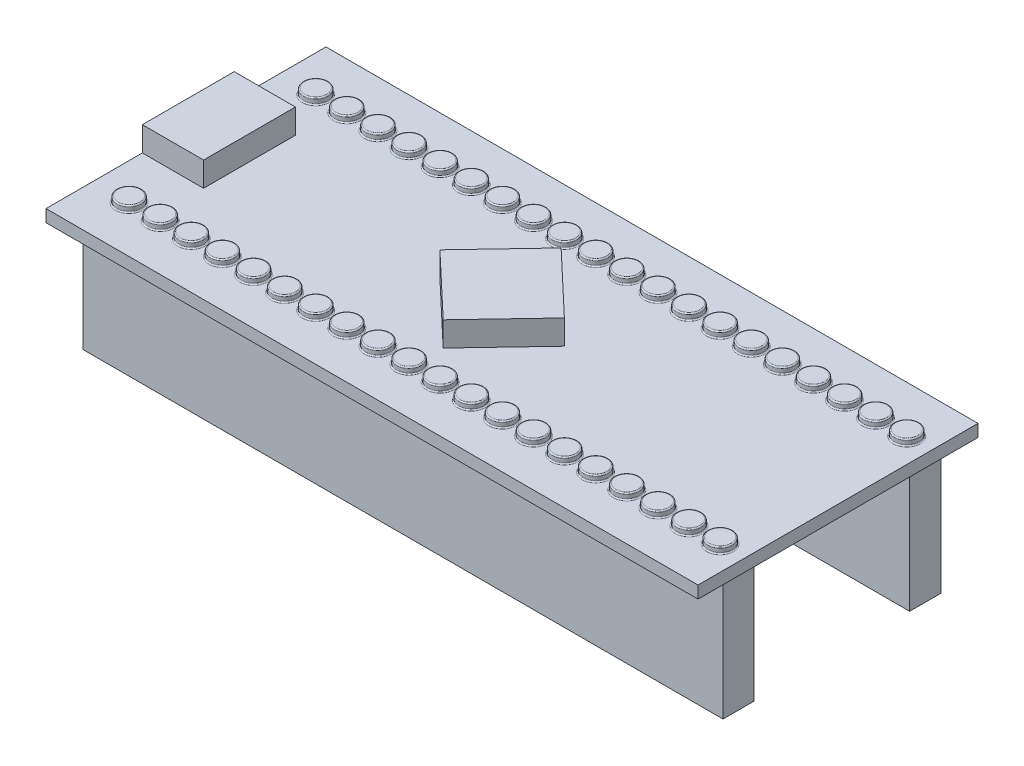
SolidWorks part; units mm, degrees
note: '?' marks a value the reader was unsure of.
ref_plane "Спереди" through (0, 0, 0) normal (0, 0, 1) x (1, 0, 0)
ref_plane "Сверху" through (0, 0, 0) normal (0, 1, 0) x (1, 0, 0)
ref_plane "Справа" through (0, 0, 0) normal (1, 0, 0) x (0, 0, -1)
sketch "Sketch1" plane through (0, 0, 0) normal (0, 1, 0) x (1, 0, 0)
  line L1 (0, 0) -> (53.24, 0)
  line L2 (0, 0) -> (0, 22.86)
  line L3 (0, 22.86) -> (53.24, 22.86)
  line L4 (53.24, 0) -> (53.24, 22.86)
  dimension "D1" = 53.24
  dimension "D2" = 22.86
extrude "Boss-Extrude1" add sketch "Sketch1" along normal blind 1
sketch "Sketch2" plane through (0, 1, 0) normal (0, 1, 0) x (1, 0, 0)
  line L0 (0, 0) -> (53.24, 0) construction
  circle A0 centre (2.9742, 3.81) radius 1
  point P4 (0, 0)
  dimension "D2" = 2
  dimension "D1" = 3.81
extrude "Boss-Extrude2" add sketch "Sketch2" along normal blind 0.5
sketch "Sketch3" plane through (0, 0, 0) normal (0, -1, 0) x (-1, 0, 0)
  line L1 (-0.5, 2.54) -> (-52.74, 2.54)
  line L2 (-0.5, 2.54) -> (-0.5, 5.08)
  line L3 (-0.5, 5.08) -> (-52.74, 5.08)
  line L4 (-52.74, 2.54) -> (-52.74, 5.08)
  line L5 (-0.5, 20.32) -> (-52.74, 20.32)
  line L6 (-0.5, 20.32) -> (-0.5, 17.78)
  line L7 (-0.5, 17.78) -> (-52.74, 17.78)
  line L8 (-52.74, 20.32) -> (-52.74, 17.78)
  line L9 (0, 0) -> (-53.24, 0) construction
  line L10 (0, 22.86) -> (0, 0) construction
  line L11 (-53.24, 0) -> (-53.24, 22.86) construction
  point P8 (-0.5, 3.81)
  point P9 (-0.5, 19.05)
  dimension "D5" = 0.5
  dimension "D1" = 15.24
  dimension "D2" = 2.54
  dimension "D3" = 2.54
  dimension "D4" = 3.81
  dimension "D6" = 0.5
  dimension "D7" = 0.5
extrude "Boss-Extrude3" add sketch "Sketch3" along normal blind 10
pattern_linear "LPattern1" count 20 spacing 2.54 along (1, 0, 0) of "Boss-Extrude2"
fillet "Fillet1" radius 0.1 1 edges at (2.9742, 1.5, -2.81)
fillet "Fillet2" radius 0.1 38 edges at (5.5142, 1.5, -2.81) (5.5142, 1, -4.81) (8.0542, 1, -4.81) (8.0542, 1.5, -2.81) (10.5942, 1, -4.81) (10.5942, 1.5, -2.81) (13.1342, 1, -4.81) (13.1342, 1.5, -2.81) (15.6742, 1, -4.81) (15.6742, 1.5, -2.81) (18.2142, 1, -4.81) (18.2142, 1.5, -2.81) (20.7542, 1, -4.81) (20.7542, 1.5, -2.81) (23.2942, 1, -4.81) (23.2942, 1.5, -2.81) (25.8342, 1, -4.81) (25.8342, 1.5, -2.81) (28.3742, 1, -4.81) (28.3742, 1.5, -2.81) (30.9142, 1, -4.81) (30.9142, 1.5, -2.81) (33.4542, 1, -4.81) (33.4542, 1.5, -2.81) (35.9942, 1, -4.81) (35.9942, 1.5, -2.81) (38.5342, 1, -4.81) (38.5342, 1.5, -2.81) (41.0742, 1, -4.81) (41.0742, 1.5, -2.81) (43.6142, 1, -4.81) (43.6142, 1.5, -2.81) (46.1542, 1, -4.81) (46.1542, 1.5, -2.81) (48.6942, 1, -4.81) (48.6942, 1.5, -2.81) (51.2342, 1, -4.81) (51.2342, 1.5, -2.81)
fillet "Fillet3" radius 0.1 1 edges at (2.9742, 1, -4.81)
pattern_linear "LPattern2" count 2 spacing 15.24 along (0, 0, -1) of "LPattern1", "Boss-Extrude2"
fillet "Fillet4" radius 0.1 41 edges at (2.9742, 1, -20.05) (2.9742, 1.5, -18.05) (5.5142, 1, -20.05) (5.5142, 1.5, -18.05) (8.0542, 1, -20.05) (8.0542, 1.5, -18.05) (10.5942, 1, -20.05) (10.5942, 1.5, -18.05) (13.1342, 1, -20.05) (13.1342, 1.5, -18.05) (15.6742, 1, -20.05) (15.6742, 1.5, -18.05) (18.2142, 1, -20.05) (18.2142, 1.5, -18.05) (20.7542, 1, -20.05) (20.7542, 1.5, -18.05) (23.2942, 1, -20.05) (23.2942, 1.5, -18.05) (25.8342, 1, -20.05) (25.8342, 1.5, -18.05) (28.3742, 1, -20.05) (28.3742, 1.5, -18.05) (30.9142, 1, -20.05) (30.9142, 1.5, -18.05) (33.4542, 1, -20.05) (33.4542, 1.5, -18.05) (35.9942, 1, -20.05) (35.9942, 1.5, -18.05) (38.5342, 1, -20.05) (38.5342, 1.5, -18.05) (41.0742, 1, -20.05) (41.0742, 1.5, -18.05) (43.6142, 1, -20.05) (43.6142, 1.5, -18.05) (46.1542, 1, -20.05) (46.1542, 1.5, -18.05) (48.6942, 1, -20.05) (48.6942, 1.5, -18.05) (51.2342, 1, -20.05) (51.2342, 1.5, -18.05) (26.62, 0, -20.32)
ref_axis "Axis1" through (0, 1, -11.43) along (1, 0, 0)?
sketch "Sketch5" plane through (0, 1, 0) normal (0, 1, 0) x (1, 0, 0)
  line L0 (0, 22.86) -> (0, 0) construction
  line L1 (5, 15.3666) -> (0, 15.3666)
  line L2 (5, 15.3666) -> (5, 7.8666)
  line L3 (5, 7.8666) -> (0, 7.8666)
  line L4 (0, 15.3666) -> (0, 7.8666)
  dimension "D1" = 5
  dimension "D2" = 7.5
extrude "Boss-Extrude4" add sketch "Sketch5" along normal blind 2 separate body
sketch "Sketch6" plane through (0, 1, 0) normal (0, 1, 0) x (1, 0, 0)
  line L0 (25.8151, 16.2451) -> (21, 11.1642)
  line L1 (25.8151, 16.2451) -> (30.8959, 11.43)
  line L2 (21, 11.1642) -> (26.0809, 6.3491)
  line L3 (30.8959, 11.43) -> (26.0809, 6.3491)
  line L5 (0, 22.86) -> (0, 0) construction
  point P0 (31.3637, 11.43)
  dimension "D1" = 7
  dimension "D2" = 7
  dimension "D3" = 21
extrude "Boss-Extrude5" add sketch "Sketch6" along normal blind 2
